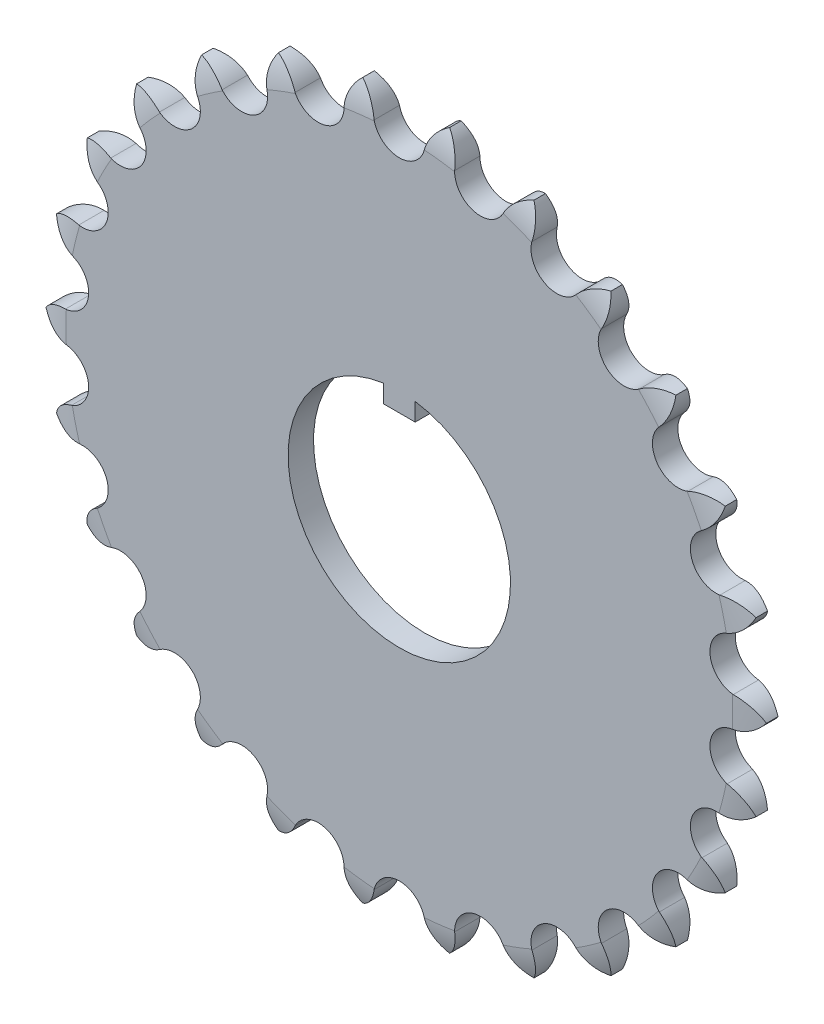
SolidWorks part; units mm, degrees
material "Plain Carbon Steel"
ref_plane "Front Plane" through (0, 0, 0) normal (0, 0, 1) x (1, 0, 0)
ref_plane "Top Plane" through (0, 0, 0) normal (0, 1, 0) x (1, 0, 0)
ref_plane "Right Plane" through (0, 0, 0) normal (1, 0, 0) x (0, 0, -1)
sketch "Sketch2" plane through (0, 0, 0) normal (0, 0, 1) x (1, 0, 0)
  line L0 (0, 0) -> (0, 79.9625) construction
  line L1 (0, 0) -> (9.6643, 51.1653) construction
  circle A0 centre (0, 0) radius 56.769 construction
  circle A1 centre (0, 0) radius 53.34 construction
  circle A2 centre (0, 0) radius 52.07 construction
  arc A3 (-3.9649, 52.4478) -> (3.9649, 52.4478) centre (0, 53.34) ccw
  arc A4 (-6.9555, 56.3413) -> (-3.9649, 52.4478) centre (-9.6643, 51.1653) cw
  arc A5 (6.9555, 56.3413) -> (3.9649, 52.4478) centre (9.6643, 51.1653) ccw
  arc A6 (6.73, 56.3687) -> (8.7019, 51.8726) centre (2.8611, 51.9913) cw
  arc A7 (8.7019, 51.8726) -> (16.4012, 49.9749) centre (12.7651, 51.79) ccw
  arc A8 (20.2367, 53.0396) -> (16.4012, 49.9749) centre (21.6282, 47.3657) ccw
  arc A9 (20.0243, 53.1201) -> (20.863, 48.2828) centre (15.2203, 49.7958) cw
  arc A10 (20.863, 48.2828) -> (27.8844, 44.5977) centre (24.7883, 47.2302) ccw
  arc A11 (32.3419, 46.6554) -> (27.8844, 44.5977) centre (32.335, 40.8134) ccw
  arc A12 (32.1549, 46.7844) -> (31.8116, 41.8869) centre (26.695, 44.7064) cw
  arc A13 (31.8116, 41.8869) -> (37.7471, 36.6286) centre (35.371, 39.9256) ccw
  arc A14 (42.5674, 37.5597) -> (37.7471, 36.6286) centre (41.1627, 31.8891) ccw
  arc A15 (42.4168, 37.7298) -> (40.9114, 33.0568) centre (36.6182, 37.0188) cw
  arc A16 (40.9114, 33.0568) -> (45.416, 26.5307) centre (43.898, 30.3006) ccw
  arc A17 (50.3191, 26.2812) -> (45.416, 26.5307) centre (47.5982, 21.1116) ccw
  arc A18 (50.2136, 26.4824) -> (47.6336, 22.3055) centre (44.4133, 27.1798) cw
  arc A19 (47.6336, 22.3055) -> (50.4455, 14.891) centre (49.8738, 18.9146) ccw
  arc A20 (55.1465, 13.4754) -> (50.4455, 14.891) centre (51.2674, 9.1071) ccw
  arc A21 (55.0921, 13.696) -> (51.5875, 10.2578) centre (49.6273, 15.7612) cw
  arc A22 (51.5875, 10.2578) -> (52.5433, 2.3859) centre (52.9511, 6.4294) ccw
  arc A23 (56.7689, -0.1136) -> (52.5433, 2.3859) centre (51.9571, -3.4266) ccw
  arc A24 (56.7689, 0.1136) -> (52.5433, -2.3859) centre (51.9571, 3.4266) cw
  arc A25 (52.5433, -2.3859) -> (51.5875, -10.2578) centre (52.9511, -6.4294) ccw
  arc A26 (55.0921, -13.696) -> (51.5875, -10.2578) centre (49.6273, -15.7612) ccw
  arc A27 (55.1465, -13.4754) -> (50.4455, -14.891) centre (51.2674, -9.1071) cw
  arc A28 (50.4455, -14.891) -> (47.6336, -22.3055) centre (49.8738, -18.9146) ccw
  arc A29 (50.2136, -26.4824) -> (47.6336, -22.3055) centre (44.4133, -27.1798) ccw
  arc A30 (50.3191, -26.2812) -> (45.416, -26.5307) centre (47.5982, -21.1116) cw
  arc A31 (45.416, -26.5307) -> (40.9114, -33.0568) centre (43.898, -30.3006) ccw
  arc A32 (42.4168, -37.7298) -> (40.9114, -33.0568) centre (36.6182, -37.0188) ccw
  arc A33 (42.5674, -37.5597) -> (37.7471, -36.6286) centre (41.1627, -31.8891) cw
  arc A34 (37.7471, -36.6286) -> (31.8116, -41.8869) centre (35.371, -39.9256) ccw
  arc A35 (32.1549, -46.7844) -> (31.8116, -41.8869) centre (26.695, -44.7064) ccw
  arc A36 (32.3419, -46.6554) -> (27.8844, -44.5977) centre (32.335, -40.8134) cw
  arc A37 (27.8844, -44.5977) -> (20.863, -48.2828) centre (24.7883, -47.2302) ccw
  arc A38 (20.0243, -53.1201) -> (20.863, -48.2828) centre (15.2203, -49.7958) ccw
  arc A39 (20.2367, -53.0396) -> (16.4012, -49.9749) centre (21.6282, -47.3657) cw
  arc A40 (16.4012, -49.9749) -> (8.7019, -51.8726) centre (12.7651, -51.79) ccw
  arc A41 (6.73, -56.3687) -> (8.7019, -51.8726) centre (2.8611, -51.9913) ccw
  arc A42 (6.9555, -56.3413) -> (3.9649, -52.4478) centre (9.6643, -51.1653) cw
  arc A43 (3.9649, -52.4478) -> (-3.9649, -52.4478) centre (0, -53.34) ccw
  arc A44 (-6.9555, -56.3413) -> (-3.9649, -52.4478) centre (-9.6643, -51.1653) ccw
  arc A45 (-6.73, -56.3687) -> (-8.7019, -51.8726) centre (-2.8611, -51.9913) cw
  arc A46 (-8.7019, -51.8726) -> (-16.4012, -49.9749) centre (-12.7651, -51.79) ccw
  arc A47 (-20.2367, -53.0396) -> (-16.4012, -49.9749) centre (-21.6282, -47.3657) ccw
  arc A48 (-20.0243, -53.1201) -> (-20.863, -48.2828) centre (-15.2203, -49.7958) cw
  arc A49 (-20.863, -48.2828) -> (-27.8844, -44.5977) centre (-24.7883, -47.2302) ccw
  arc A50 (-32.3419, -46.6554) -> (-27.8844, -44.5977) centre (-32.335, -40.8134) ccw
  arc A51 (-32.1549, -46.7844) -> (-31.8116, -41.8869) centre (-26.695, -44.7064) cw
  arc A52 (-31.8116, -41.8869) -> (-37.7471, -36.6286) centre (-35.371, -39.9256) ccw
  arc A53 (-42.5674, -37.5597) -> (-37.7471, -36.6286) centre (-41.1627, -31.8891) ccw
  arc A54 (-42.4168, -37.7298) -> (-40.9114, -33.0568) centre (-36.6182, -37.0188) cw
  arc A55 (-40.9114, -33.0568) -> (-45.416, -26.5307) centre (-43.898, -30.3006) ccw
  arc A56 (-50.3191, -26.2812) -> (-45.416, -26.5307) centre (-47.5982, -21.1116) ccw
  arc A57 (-50.2136, -26.4824) -> (-47.6336, -22.3055) centre (-44.4133, -27.1798) cw
  arc A58 (-47.6336, -22.3055) -> (-50.4455, -14.891) centre (-49.8738, -18.9146) ccw
  arc A59 (-55.1465, -13.4754) -> (-50.4455, -14.891) centre (-51.2674, -9.1071) ccw
  arc A60 (-55.0921, -13.696) -> (-51.5875, -10.2578) centre (-49.6273, -15.7612) cw
  arc A61 (-51.5875, -10.2578) -> (-52.5433, -2.3859) centre (-52.9511, -6.4294) ccw
  arc A62 (-56.7689, 0.1136) -> (-52.5433, -2.3859) centre (-51.9571, 3.4266) ccw
  arc A63 (-56.7689, -0.1136) -> (-52.5433, 2.3859) centre (-51.9571, -3.4266) cw
  arc A64 (-52.5433, 2.3859) -> (-51.5875, 10.2578) centre (-52.9511, 6.4294) ccw
  arc A65 (-55.0921, 13.696) -> (-51.5875, 10.2578) centre (-49.6273, 15.7612) ccw
  arc A66 (-55.1465, 13.4754) -> (-50.4455, 14.891) centre (-51.2674, 9.1071) cw
  arc A67 (-50.4455, 14.891) -> (-47.6336, 22.3055) centre (-49.8738, 18.9146) ccw
  arc A68 (-50.2136, 26.4824) -> (-47.6336, 22.3055) centre (-44.4133, 27.1798) ccw
  arc A69 (-50.3191, 26.2812) -> (-45.416, 26.5307) centre (-47.5982, 21.1116) cw
  arc A70 (-45.416, 26.5307) -> (-40.9114, 33.0568) centre (-43.898, 30.3006) ccw
  arc A71 (-42.4168, 37.7298) -> (-40.9114, 33.0568) centre (-36.6182, 37.0188) ccw
  arc A72 (-42.5674, 37.5597) -> (-37.7471, 36.6286) centre (-41.1627, 31.8891) cw
  arc A73 (-37.7471, 36.6286) -> (-31.8116, 41.8869) centre (-35.371, 39.9256) ccw
  arc A74 (-32.1549, 46.7844) -> (-31.8116, 41.8869) centre (-26.695, 44.7064) ccw
  arc A75 (-32.3419, 46.6554) -> (-27.8844, 44.5977) centre (-32.335, 40.8134) cw
  arc A76 (-27.8844, 44.5977) -> (-20.863, 48.2828) centre (-24.7883, 47.2302) ccw
  arc A77 (-20.0243, 53.1201) -> (-20.863, 48.2828) centre (-15.2203, 49.7958) ccw
  arc A78 (-20.2367, 53.0396) -> (-16.4012, 49.9749) centre (-21.6282, 47.3657) cw
  arc A79 (-16.4012, 49.9749) -> (-8.7019, 51.8726) centre (-12.7651, 51.79) ccw
  arc A80 (-6.73, 56.3687) -> (-8.7019, 51.8726) centre (-2.8611, 51.9913) ccw
  circle A81 centre (0, 0) radius 17.5
  point P8 (0, 0)
  point P191 (0, 0)
  dimension "D1" = 113.538
  dimension "D2" = 106.68
  dimension "D3" = 104.14
  dimension "D4" = 8.128
  dimension "D5" = 5.842
  dimension "D7" = 35
  dimension "D6" = 26
extrude "Boss-Extrude1" add sketch "Sketch2" along normal blind 4 contours A4 A80 A79 A78 A77 A76 A75 A74 A73 A72 A71 A70 A69 A68 A67 A66 A65 A64 A63 A62 A61 A60 A59 A58 A57 A56 A55 A54 A53 A52 A51 A50 A49 A48 A47 A46 A45 A44 A43 A42 A41 A40 A39 A38 A37 A36 A35 A34 A33 A32 A31 region at (0, 47.6784, 0)
sketch "Sketch7" plane through (0, 0, 0) normal (1, 0, 0) x (0, 0, -1)
  line L0 (-2, 56.2754) -> (-2, 49.8539) construction
  line L1 (-4, 56.2754) -> (0, 56.2754) construction
  line L2 (-2.4125, 56.2754) -> (-2.4125, 50.2263) construction
  line L3 (-4, 53.0048) -> (-4, 48.2828) construction
  line L4 (-4, 50.419) -> (-7.7746, 50.419)
  line L5 (-7.7746, 50.419) -> (-7.7746, 56.896)
  line L6 (-7.7746, 56.896) -> (-2.8088, 56.896)
  line L7 (-1.5875, 56.2754) -> (-1.5875, 50.2263) construction
  line L8 (3.7746, 56.896) -> (-1.1912, 56.896)
  line L9 (3.7746, 50.419) -> (3.7746, 56.896)
  line L10 (0, 50.419) -> (3.7746, 50.419)
  line L11 (0, 0) -> (92.826, 0) construction
  arc A0 (-2.8088, 56.896) -> (-4, 50.419) centre (8.659, 51.4389) ccw
  arc A1 (-1.1912, 56.896) -> (0, 50.419) centre (-12.659, 51.4389) cw
  dimension "D2" = 12.7
  dimension "D1" = 1.5875
  dimension "D3" = 50.419
  dimension "D4" = 56.896
revolve "Cut-Revolve1" cut sketch "Sketch7" angle 360 about L11
ref_plane "Plane1" through (0, 0, 2) normal (0, 0, 1) x (1, 0, 0)
sketch "Sketch8" plane through (0, 0, 2) normal (0, 0, 1) x (1, 0, 0)
  line L0 (2.5, 14.5) -> (-2.5, 14.5)
  line L3 (2.5, 14.5) -> (2.5, 22.4506)
  line L4 (2.5, 22.4506) -> (-2.5, 22.4506)
  line L5 (-2.5, 14.5) -> (-2.5, 22.4506)
extrude "Boss-Extrude2" add sketch "Sketch8" along normal blind 2 and the other way blind 2 contours L0 L5 L4 L3
